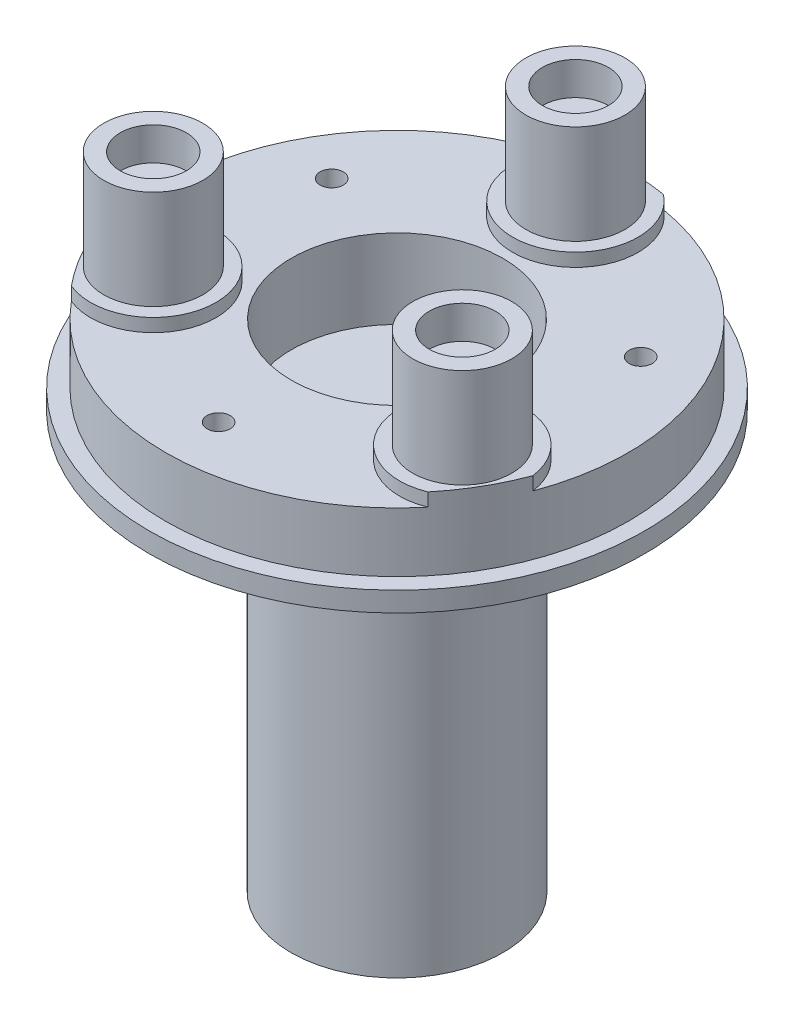
SolidWorks part; units mm, degrees
note: The reader was unsure of these and kept them because the rebuilt part matched: shared geometry of "Sketch1<3>".
ref_plane "Front Plane" through (0, 0, 0) normal (0, 0, 1) x (1, 0, 0)
ref_plane "Top Plane" through (0, 0, 0) normal (0, 1, 0) x (1, 0, 0)
ref_plane "Right Plane" through (0, 0, 0) normal (1, 0, 0) x (0, 0, -1)
sketch "Sketch1" plane through (0, 0, 0) normal (0, 1, 0) x (1, 0, 0)
  line L0 (0, 0) -> (0, 44.6523) construction
  circle A4 centre (0, 0) radius 37.5
  circle A5 centre (0, 0) radius 35
  arc A6 (-10.4425, 33.4059) -> (10.4425, 33.4059) centre (0, 30) ccw
  circle A7 centre (0, 0) radius 35
  arc A8 (34.1516, -7.6594) -> (23.7091, -25.7465) centre (25.9808, -15) ccw
  arc A9 (-23.7091, -25.7465) -> (-34.1516, -7.6594) centre (-25.9808, -15) ccw
  point P17 (0, 0)
  dimension "D1" = 75
  dimension "D2" = 70
  dimension "D3" = 30
  dimension "D4" = 3
extrude "Boss-Extrude1" add sketch "Sketch1" along normal blind 3 contours A4
extrude "Boss-Extrude2" add sketch "Sketch1<3>" along normal blind 12
sketch "Sketch1<3>" plane through (0, 0, 0) normal (0, 1, 0) x (1, 0, 0) same geometry as "Sketch1"
sketch "Sketch13" plane through (0, 12, 0) normal (0, 1, 0) x (1, 0, 0)
  circle A0 centre (0, 0) radius 16
  dimension "D1" = 32
extrude "Cut-Extrude6" cut sketch "Sketch13" against normal through all
sketch "Sketch24" plane through (0, 12, 0) normal (0, 1, 0) x (1, 0, 0)
  line L0 (0, 0) -> (0, 27.027) construction
  arc A0 (-5.813, 34.5139) -> (5.813, 34.5139) centre (0, 27) ccw
  circle A1 centre (0, 0) radius 35
  arc A2 (32.7964, -12.2227) -> (26.9834, -22.2912) centre (23.3827, -13.5) ccw
  arc A3 (-26.9834, -22.2912) -> (-32.7964, -12.2227) centre (-23.3827, -13.5) ccw
  point P15 (0, 0)
  dimension "D1" = 19
  dimension "D4" = 70
  dimension "D2" = 27
  dimension "D3" = 3
extrude "Boss-Extrude9" add sketch "Sketch24" along normal blind 2
sketch "Sketch25" plane through (0, 14, 0) normal (0, 1, 0) x (1, 0, 0)
  line L0 (0, 0) -> (0, 55.8426) construction
  circle A0 centre (0, 27) radius 7.5
  circle A1 centre (23.3827, -13.5) radius 7.5
  circle A2 centre (-23.3827, -13.5) radius 7.5
  point P11 (0, 0)
  dimension "D2" = 15
  dimension "D1" = 27
  dimension "D3" = 3
extrude "Boss-Extrude10" add sketch "Sketch25" along normal blind 15
sketch "Sketch26" plane through (0, 29, 0) normal (0, 1, 0) x (1, 0, 0)
  line L0 (0, 0) -> (0, 38.3857) construction
  circle A0 centre (0, 27) radius 5
  circle A1 centre (23.3827, -13.5) radius 5
  circle A2 centre (-23.3827, -13.5) radius 5
  point P11 (0, 0)
  dimension "D2" = 10
  dimension "D1" = 27
  dimension "D3" = 3
extrude "Cut-Extrude9" cut sketch "Sketch26" against normal blind 5
hole_wizard "CBORE for M3 Pan Head Machine Screw1" positions "Sketch27" profile "Sketch28" counterbore size "M3" standard "ANSI Metric" end condition through all
sketch "Sketch27" plane through (0, 0, 0) normal (0, -1, 0) x (-1, 0, 0)
  point P0 (0, 27)
  point P9 (23.3827, -13.5)
  point P10 (-23.3827, -13.5)
  dimension "D1" = 27
  dimension "D2" = 3
sketch "Sketch28" plane through (0, 0, -27) normal (1, 0, 0) x (0, 0, -1)
  line L0 (0, 0) -> (0, 29)
  line L1 (0, 29) -> (1.8, 29)
  line L3 (1.8, 29) -> (1.8, 2.4)
  line L4 (3.5, 2.4) -> (1.8, 2.4)
  line L5 (3.5, 2.4) -> (3.5, 0.025)
  line L6 (3.5, 0.025) -> (3.525, 0)
  line L7 (3.525, 0) -> (0, 0)
  line L8 (-3.5, 0.025) -> (-3.525, 0) construction
  line L11 (0, -6.35) -> (0, 107.95) construction
  dimension "Thru Hole Dia." = 3.6
  dimension "Thru Hole Depth" = 29
  dimension "C'Bore Dia." = 7
  dimension "C'Bore Depth" = 2.4
  dimension "Near C'Sink Dia." = 7.05
  dimension "Near C'Sink Angle" = 90
sketch "Sketch29" plane through (0, 12, 0) normal (0, 1, 0) x (1, 0, 0)
  line L0 (0, 0) -> (23.3827, 13.5) construction
  line L1 (0, 0) -> (0, 14.4601) construction
  circle A0 centre (23.3827, 13.5) radius 1.75
  circle A1 centre (0, -27) radius 1.75
  circle A2 centre (-23.3827, 13.5) radius 1.75
  point P11 (0, 0)
  dimension "D3" = 3.5
  dimension "D1" = 60
  dimension "D2" = 27
  dimension "D4" = 3
extrude "Cut-Extrude10" cut sketch "Sketch29" against normal through all
sketch "Sketch30" plane through (0, 12, 0) normal (0, -1, 0) x (1, 0, 0)
  circle A0 centre (0, 0) radius 16
sketch "Sketch31" plane through (0, 0, 0) normal (0, -1, 0) x (1, 0, 0)
  circle A0 centre (0, 0) radius 16.05
  point P3 (0, 0)
extrude "Boss-Extrude11" add sketch "Sketch31" along normal blind 63 separate body
